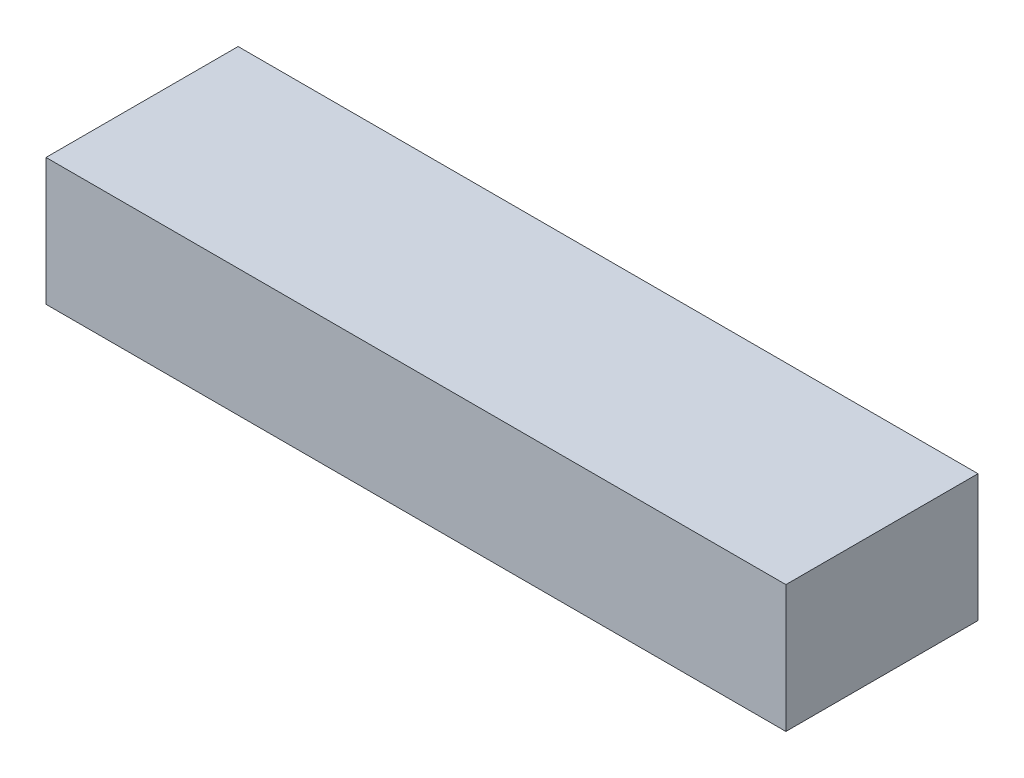
SolidWorks part; units mm, degrees
ref_plane "Front Plane" through (0, 0, 0) normal (0, 0, 1) x (1, 0, 0)
ref_plane "Top Plane" through (0, 0, 0) normal (0, 1, 0) x (1, 0, 0)
ref_plane "Right Plane" through (0, 0, 0) normal (1, 0, 0) x (0, 0, -1)
sketch "Sketch1" plane through (0, 0, 0) normal (0, 1, 0) x (1, 0, 0)
  line L1 (570, -148) -> (-570, -148)
  line L2 (570, -148) -> (570, 148)
  line L3 (570, 148) -> (-570, 148)
  line L4 (-570, -148) -> (-570, 148)
  line L5 (570, -148) -> (-570, 148) construction
  line L6 (570, 148) -> (-570, -148) construction
  point P0 (0, 0)
  dimension "D1" = 1140
  dimension "D2" = 296
extrude "Boss-Extrude1" add sketch "Sketch1" along normal blind 196
equation "\"thickness 1\"= 2"
equation "\"thickness 2\"= 3"
equation "\"connecting flange\"= 35"
equation "\"main length\"= 1200"
equation "\"main width\"= 1200"
equation "\"divider panel distance offset\"= 296"
equation "\"side panel length\"= 1200"
equation "\"side panel width\"= 950"
equation "\"drift eliminator size offset\"= 10"
equation "\"D2@Sketch1\"=\"drift eliminator depth\""
equation "\"thickness radius 1\"= 3.7366"
equation "\"connecting flange holes\"= 8"
equation "\"connecting flange hole gap\"= 100"
equation "\"cut out flange\"= 15 "
equation "\"top panel slot length\"= 250"
equation "\"top panel slot width\"= 700"
equation "\"access hatch cutout length\"= 400"
equation "\"access hatch cutout width\"= 600"
equation "\"access hatch cutout offset X\"= 100"
equation "\"access hatch cutout offset Y\"= 100"
equation "\"slot count x\"= 3"
equation "\"slot count y\"= 11"
equation "\"slot length\"= 30"
equation "\"slot width\"= 200"
equation "\"guide rail flange\"= 40"
equation "\"guid rail flange mount side\"= 20"
equation "\"splash plate length\"= 400"
equation "\"splash plate air gap\"= 200"
equation "\"splash plate slot count\"= 11"
equation "\"splash plate slot length\"= 50"
equation "\"splash plate slot height\"= 50"
equation "\"splash plate slot offset\"= 65"
equation "\"water tray depth\"= 150"
equation "\"water tray width\"= 200"
equation "\"water tray panel length\"= 473"
equation "\"dimple panel slot count\"= 119"
equation "\"dimple panel slot length\"= 10"
equation "\"dimple panel slot width\"= 5"
equation "\"dimple panel slot offset\"= 10"
equation "\"sump base flat section width\"= 300"
equation "\"sump upper depth\"= 300"
equation "\"sump depth\"= 550"
equation "\"leg width\"= 80"
equation "\"leg depth\"= 40"
equation "\"leg base plate thickness\"= 8"
